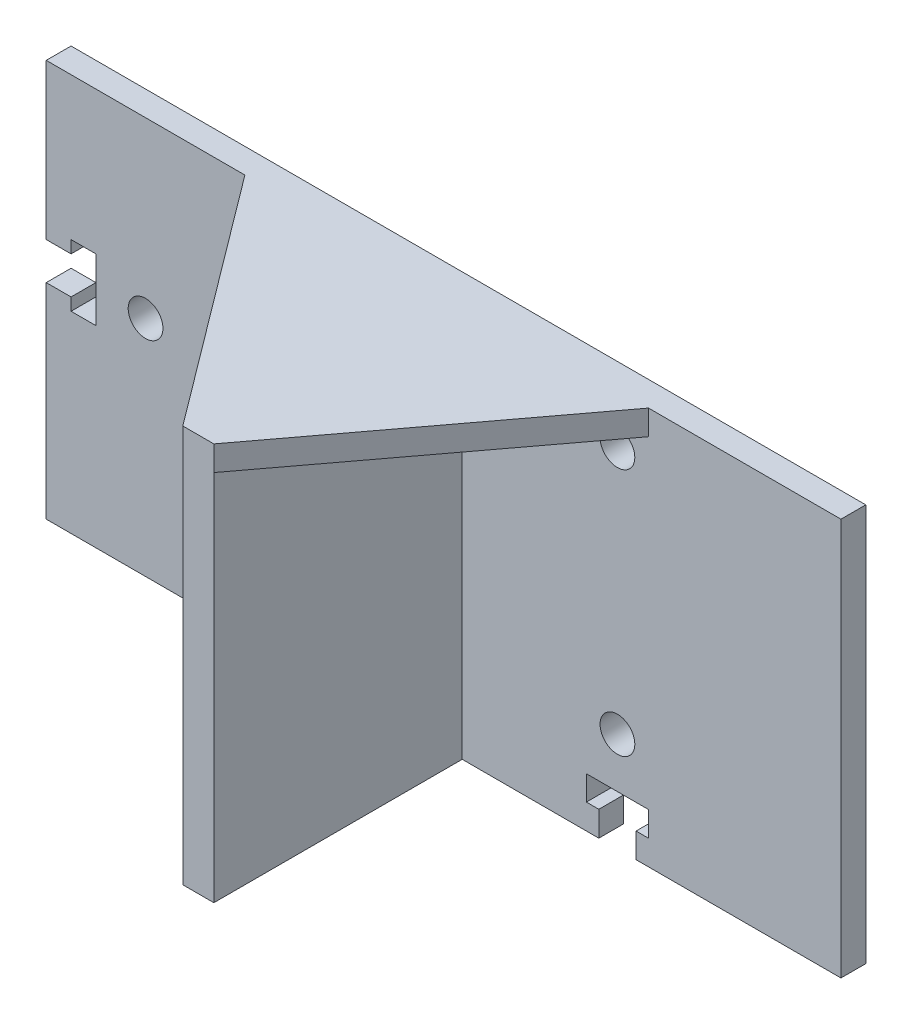
SolidWorks part; units mm, degrees
ref_plane "Plan de face" through (0, 0, 0) normal (0, 0, 1) x (1, 0, 0)
ref_plane "Plan de dessus" through (0, 0, 0) normal (0, 1, 0) x (1, 0, 0)
ref_plane "Plan de droite" through (0, 0, 0) normal (1, 0, 0) x (0, 0, -1)
sketch "Esquisse1" plane through (0, 0, 0) normal (0, 0, 1) x (1, 0, 0)
  line L1 (0, 0) -> (43.5, 0)
  line L3 (0, 32) -> (64, 32)
  line L4 (64, 0) -> (64, 32)
  line L17 (0, 32) -> (0, 19.5)
  line L21 (0, 13.5) -> (0, 0)
  line L22 (2, 20.5) -> (4, 20.5)
  line L24 (2, 15.5) -> (4, 15.5)
  line L25 (4, 20.5) -> (4, 15.5)
  line L27 (2, 19.5) -> (2, 20.5)
  line L28 (0, 19.5) -> (2, 19.5)
  line L30 (0, 16.5) -> (2, 16.5)
  line L32 (2, 16.5) -> (2, 15.5)
  line L33 (0, 16.5) -> (0, 13.5)
  line L34 (48.5, 0) -> (64, 0)
  line L35 (43.5, 4) -> (48.5, 4)
  line L36 (43.5, 4) -> (43.5, 2.0182)
  line L38 (48.5, 4) -> (48.5, 2)
  line L39 (43.5, 4) -> (46, 0) construction
  line L40 (46, 0) -> (48.5, 4) construction
  line L42 (43.5, 0) -> (44.5, 0)
  line L44 (43.5, 2.0182) -> (44.5, 2.0182)
  line L45 (44.5, 0) -> (44.5, 2.0182)
  line L46 (48.5, 2) -> (47.5, 2)
  line L48 (48.5, 0) -> (47.5, 0)
  line L49 (47.5, 2) -> (47.5, 0)
  point P5 (0, 16)
  point P10 (0, 16)
  point P12 (46, 0)
  point P14 (-4, 14)
  point P22 (0, 18)
  point P25 (0, 10)
  dimension "D9" = 2
  dimension "D1" = 64
  dimension "D2" = 32
  dimension "D3" = 1
  dimension "D4" = 5
  dimension "D5" = 18
  dimension "D6" = 1
  dimension "D7" = 1
  dimension "D8" = 5
  dimension "D10" = 2
  dimension "D11" = 2
  dimension "D12" = 1
  dimension "D13" = 11.5
extrude "Boss.-Extru.1" add sketch "Esquisse1" along normal blind 2
sketch "Esquisse2" plane through (0, 0, 2) normal (0, 0, 1) x (1, 0, 0)
  line L0 (64, 32) -> (0, 32) construction
  line L5 (0, 0) -> (44.5, 0) construction
  line L6 (64, 0) -> (64, 32) construction
  line L11 (47.5, 0) -> (64, 0) construction
  line L12 (64, 32) -> (0, 32) construction
  line L13 (0, 16.5) -> (0, 0) construction
  circle A0 centre (8, 18) radius 1.4
  circle A1 centre (28, 18) radius 1.4
  circle A2 centre (46, 28) radius 1.4
  circle A3 centre (46, 8) radius 1.4
  point P0 (18, 18)
  point P5 (46, 18)
  dimension "D9" = 2.8
  dimension "D10" = 2.8
  dimension "D11" = 2.8
  dimension "D12" = 2.8
  dimension "D2" = 18
  dimension "D3" = 14
  dimension "D4" = 14
  dimension "D5" = 18
  dimension "D6" = 18
  dimension "D7" = 8
  dimension "D8" = 4
  dimension "D13" = 18
  dimension "D14" = 28
  dimension "D15" = 8
sketch "Esquisse3" plane through (0, 0, 2) normal (0, 0, 1) x (1, 0, 0)
  line L0 (0, 0) -> (44.5, 0) construction
  line L1 (26.9177, 32) -> (29.4177, 32)
  line L2 (31, 30) -> (31, 0)
  line L3 (31, 0) -> (33.5, 0)
  line L4 (33.5, 30) -> (33.5, 0)
  line L5 (0, 32) -> (0, 19.5) construction
  line L7 (64, 32) -> (0, 32) construction
  line L9 (26.9177, 32) -> (16, 32)
  line L11 (31, 30) -> (16, 30)
  line L12 (16, 32) -> (16, 30)
  line L13 (29.4177, 32) -> (48.5, 32)
  line L15 (33.5, 30) -> (48.5, 30)
  line L16 (48.5, 32) -> (48.5, 30)
  point P0 (28.1677, 14)
  dimension "D1" = 2.5
  dimension "D2" = 15
  dimension "D3" = 15
  dimension "D4" = 2
  dimension "D5" = 2
  dimension "D6" = 16
extrude "Boss.-Extru.2" add sketch "Esquisse3" along normal blind 20
extrude "Enlèv. mat.-Extru.1" cut sketch "Esquisse2" against normal through all
chamfer "Chanfrein1" distance 20 distance2 15 2 edges at (48.5, 31, 22) (16, 31, 22) first distance on face at (48.5, 31, 12) first distance on face at (16, 31, 12)
